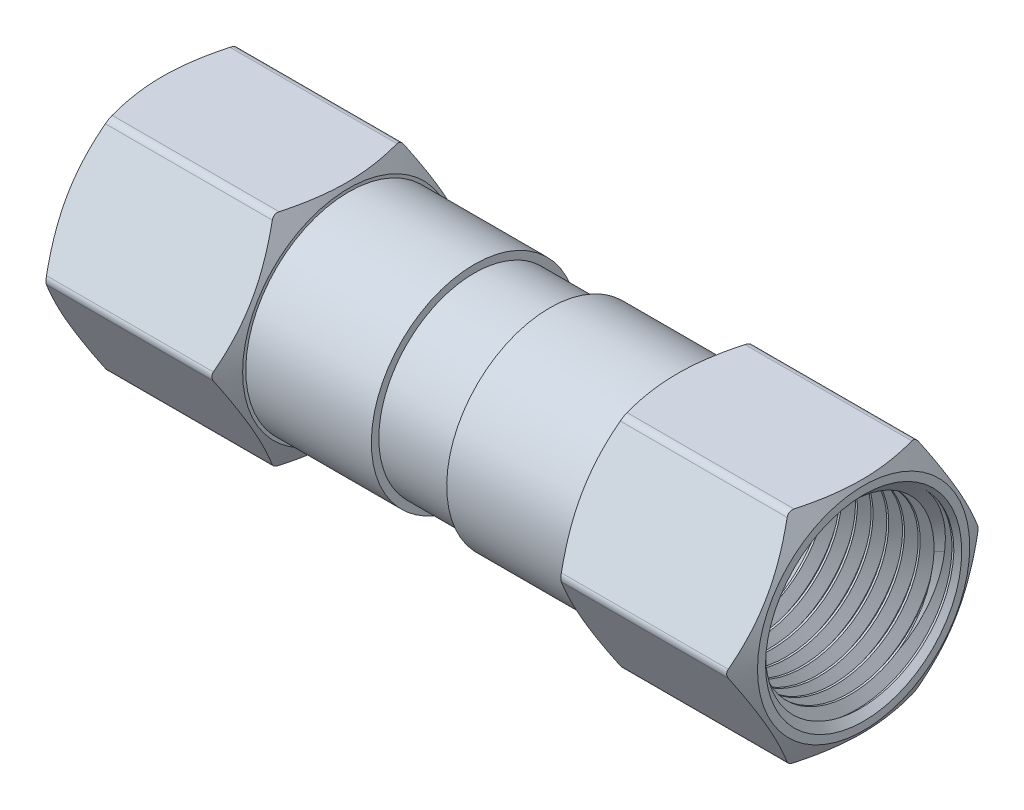
SolidWorks part; units mm, degrees
note: The reader was unsure of these and kept them because the rebuilt part matched: shared geometry of "Sketch4<2>", "Sketch8<2>".
material "AISI 304"
ref_plane "Front Plane" through (0, 0, 0) normal (0, 0, 1) x (1, 0, 0)
ref_plane "Top Plane" through (0, 0, 0) normal (0, 1, 0) x (1, 0, 0)
ref_plane "Right Plane" through (0, 0, 0) normal (1, 0, 0) x (0, 0, -1)
sketch "Sketch1" plane through (0, 0, 0) normal (0, 0, 1) x (1, 0, 0)
  line L0 (35.56, 0) -> (-35.56, 0) construction
  line L1 (-16.51, -9.525) -> (-16.51, 9.525) construction
  line L2 (-16.51, 9.525) -> (-35.56, 9.525) construction
  line L3 (0, 9.652) -> (0, -9.652) construction
  line L4 (-35.56, 9.525) -> (-35.56, 0) construction
  line L5 (-16.51, 9.525) -> (-18.0975, 9.525) construction
  line L6 (-35.56, 11.1125) -> (-16.51, 11.1125) construction
  line L7 (-16.51, 10.414) -> (-3.81, 10.414) construction
  line L12 (35.56, 9.525) -> (35.56, 0) construction
  point P3 (15.24, 0)
  point P4 (0, 0)
  point P8 (-16.51, 0)
  point P11 (0, 6.35)
  point P20 (-15.24, 0)
  dimension "Thread Size" = 19.05
  dimension "OD" = 19.304
  dimension "ID" = 12.7
  dimension "Pitch" = 1.5875
  dimension "Hex Length" = 19.05
  dimension "Hex Width" = 22.225
  dimension "Length" = 71.12
  dimension "Sleeve Length" = 12.7
  dimension "D2" = 0.762
  dimension "D1" = 19.05
sketch "Sketch2" plane through (0, 0, 0) normal (1, 0, 0) x (0, 0, -1)
  line L0 (-5.9575, -10.3187) -> (0, 0) construction
  line L1 (5.9575, 11.1125) -> (-5.9575, 11.1125)
  line L2 (-6.6449, 10.7156) -> (-12.6025, 0.3969)
  line L3 (-12.6025, -0.3969) -> (-6.6449, -10.7156)
  line L4 (-5.9575, -11.1125) -> (5.9575, -11.1125)
  line L5 (6.6449, -10.7156) -> (12.6025, -0.3969)
  line L6 (12.6025, 0.3969) -> (6.6449, 10.7156)
  circle A0 centre (0, 0) radius 11.1125 construction
  arc A1 (5.9575, -11.1125) -> (6.6449, -10.7156) centre (5.9575, -10.3187) ccw
  circle A2 centre (0, 0) radius 9.525
  arc A3 (12.6025, -0.3969) -> (12.6025, 0.3969) centre (11.9151, 0) ccw
  arc A4 (-6.6449, -10.7156) -> (-5.9575, -11.1125) centre (-5.9575, -10.3187) ccw
  arc A5 (-12.6025, 0.3969) -> (-12.6025, -0.3969) centre (-11.9151, 0) ccw
  arc A6 (-5.9575, 11.1125) -> (-6.6449, 10.7156) centre (-5.9575, 10.3187) ccw
  arc A7 (5.9575, 11.1125) -> (6.6449, 10.7156) centre (5.9575, 10.3187) cw
  point P9 (-4.7625, -8.2489)
  dimension "D1" = 0.7937
extrude "Boss-Extrude1" add sketch "Sketch2" along normal up to vertex (-16.51 mm away) from vertex at -35.56 starting at point (-35.56, 11.1125, 0)
sketch "Sketch3" plane through (-35.56, 0, 0) normal (-1, 0, 0) x (0, 0, 1)
  circle A1 centre (0, 0) radius 10.7315
  dimension "D1" = 0.381
extrude "Cut-Extrude1" cut sketch "Sketch3" against normal through all draft 60 flip side to cut
extrude "Cut-Extrude2" cut sketch "Sketch4<2>" along normal through all draft 60 from surface at -19.05 flip side to cut starting at face at (-16.51, 0, 0)
sketch "Sketch4<2>" plane through (-35.56, 0, 0) normal (-1, 0, 0) x (0, 0, 1) same geometry as "Sketch3"
sketch "Sketch5" plane through (0, 0, 0) normal (0, 0, 1) x (1, 0, 0)
  line L16 (-15.748, 6.35) -> (-15.748, 0) construction
  line L17 (-22.86, 9.525) -> (-16.51, 9.525)
  line L24 (-16.51, 9.525) -> (-16.51, 10.414)
  line L30 (-16.51, 10.414) -> (-3.81, 10.414)
  line L31 (-3.81, 9.652) -> (-15.748, 9.652)
  line L33 (-16.51, 9.525) -> (-35.56, 9.525) construction
  line L35 (-22.86, 9.525) -> (-22.86, 9.398)
  line L36 (-22.86, 9.398) -> (-18.8152, 6.35)
  line L37 (-18.8152, 6.35) -> (-15.748, 6.35)
  line L40 (-3.81, 9.652) -> (-3.81, 10.414)
  line L41 (35.56, 0) -> (-35.56, 0) construction
  line L42 (35.56, 0) -> (-35.56, 0) construction
  line L43 (-15.748, 9.652) -> (-15.748, 6.35)
  line L44 (-16.51, 9.525) -> (-15.748, 9.525) construction
  line L45 (-15.748, 9.652) -> (-15.748, 10.414) construction
  line L46 (-35.56, 10.7315) -> (-35.56, -10.7315) construction
  dimension "D3" = 12.7
  dimension "D1" = 0.127
  dimension "D2" = 37
revolve "Revolve1" add sketch "Sketch5" angle 360 about L0
mirror "Mirror1" about plane through (0, 0, 0) normal (1, 0, 0) of bodies 107 144 143
sketch "Sketch6" plane through (-15.748, 0, 0) normal (1, 0, 0) x (0, 0, -1)
  circle A5 centre (0, 0) radius 9.652
  circle A6 centre (0, 0) radius 6.35
extrude "Boss-Extrude3" add sketch "Sketch6" along normal up to surface (31.496 mm away) separate body up to face at (15.748, 9.652, 0)
sketch "Sketch8" plane through (-35.56, 0, 0) normal (-1, 0, 0) x (0, 0, 1)
  circle A0 centre (0, 0) radius 9.525 construction
  circle A1 centre (0, 0) radius 9.525
extrude "Boss-Extrude5" add sketch "Sketch8" against normal up to surface (12.7 mm away) separate body up to face at (-22.86, 9.398, 0)
extrude "Boss-Extrude6" add sketch "Sketch8<2>" against normal up to surface (12.7 mm away) up to face at (-22.86, 9.398, 0)
sketch "Sketch8<2>" plane through (-35.56, 0, 0) normal (-1, 0, 0) x (0, 0, 1) same geometry as "Sketch8"
sketch "Sketch9" plane through (-35.56, 0, 0) normal (-1, 0, 0) x (0, 0, 1)
  circle A0 centre (0, 0) radius 9.525 construction
  circle A1 centre (0, 0) radius 9.525
curve "Helix/Spiral1" pitch 1.5875 height 12.7 turns 8
sketch "Sketch10" plane through (0, 0, 0) normal (0, 0, 1) x (1, 0, 0)
  line L0 (-37.0483, 9.6969) -> (-36.2545, 8.322) construction
  line L1 (-36.2545, 8.322) -> (-35.4608, 9.6969) construction
  line L2 (-35.4608, 9.6969) -> (-37.0483, 9.6969) construction
  line L3 (-36.9491, 9.525) -> (-35.56, 9.525) construction
  line L4 (-36.2545, 9.6969) -> (-36.2545, 9.525) construction
  line L5 (-36.2545, 9.525) -> (-36.2545, 8.4939) construction
  line L6 (-36.2545, 8.4939) -> (-36.2545, 8.322) construction
  line L7 (-36.3538, 8.4939) -> (-36.1553, 8.4939)
  line L8 (-36.9987, 9.6109) -> (-35.5104, 9.6109)
  line L9 (-36.1553, 8.4939) -> (-35.5104, 9.6109)
  line L10 (-36.3538, 8.4939) -> (-36.9987, 9.6109)
  point P12 (-36.2545, 9.6109)
  dimension "D1" = 1.5875
  dimension "D2" = 0.1984
sweep "Cut-Sweep1" cut profiles "Sketch10" path "Helix/Spiral1" align with end faces yes
combine bodies "Combine1" operation type subtract main body 149 bodies to subtract 150
sketch "Sketch11" plane through (-35.56, 0, 0) normal (-1, 0, 0) x (0, 0, 1)
  circle A0 centre (0, 0) radius 9.525 construction
  circle A1 centre (0, 0) radius 9.525 construction
  circle A2 centre (0, 0) radius 9.9219
  dimension "D1" = 0.3969
extrude "Cut-Extrude3" cut sketch "Sketch11" against normal through all draft 45
delete or keep bodies "Body-Delete/Keep 1" type delete bodies bodies 146
pattern_circular "CirPattern1" count 2 over 360 about axis through (0, 9.652, 0) along (0, -1, 0) reverse direction yes of bodies 152
equation "\"D4@Helix/Spiral1\"=\"Pitch@Sketch1\""
equation "\"D2@Sketch10\"=\"D1@Sketch10\"/8"
equation "\"D1@Sketch10\"=\"Pitch@Sketch1\""
equation "\"D1@Sketch1\"=\"Thread Size@Sketch1\""
equation "\"D3@Helix/Spiral1\"=\"D3@Sketch5\""
